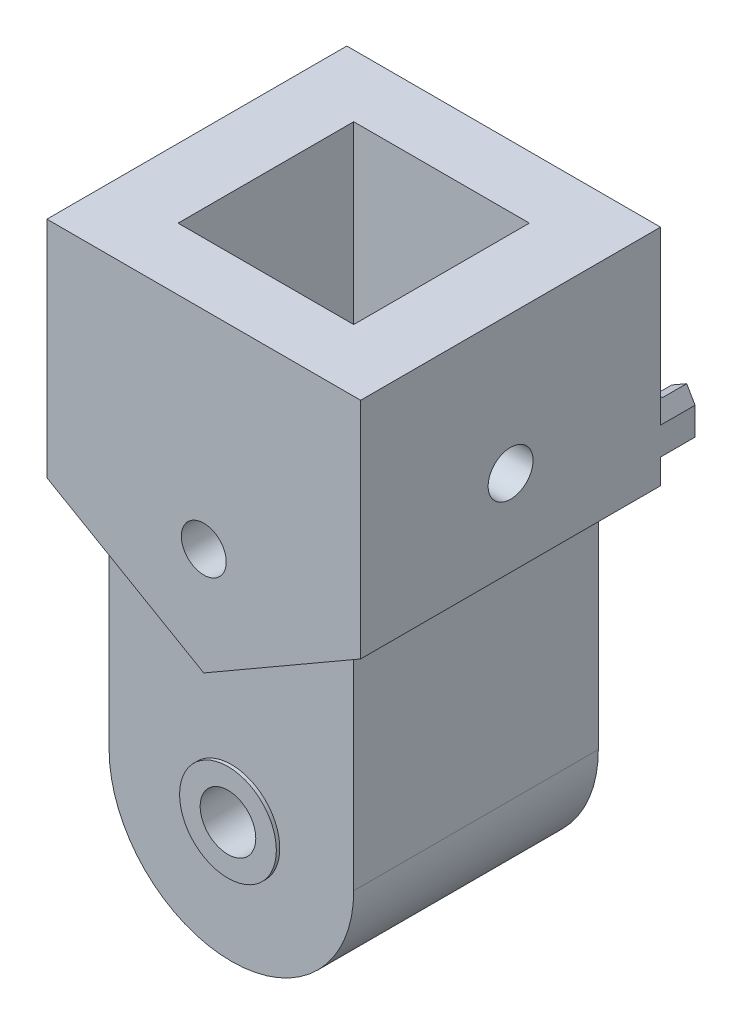
SolidWorks part; units mm, degrees
material "PETG"
ref_plane "Front Plane" through (0, 0, 0) normal (0, 0, 1) x (1, 0, 0)
ref_plane "Top Plane" through (0, 0, 0) normal (0, 1, 0) x (1, 0, 0)
ref_plane "Right Plane" through (0, 0, 0) normal (1, 0, 0) x (0, 0, -1)
sketch "Sketch1" plane through (0, 0, 0) normal (0, 1, 0) x (1, 0, 0)
  line L1 (-12.71, -12.71) -> (12.71, -12.71)
  line L2 (-12.71, -12.71) -> (-12.71, 12.71)
  line L3 (-12.71, 12.71) -> (12.71, 12.71)
  line L4 (12.71, -12.71) -> (12.71, 12.71)
  line L5 (-17.7, -17.7) -> (17.7, -17.7)
  line L6 (-17.7, -17.7) -> (-17.7, 17.7)
  line L7 (-17.7, 17.7) -> (17.7, 17.7)
  line L8 (17.7, -17.7) -> (17.7, 17.7)
  point P8 (0, -17.7)
  point P9 (0, -12.71)
  point P12 (-17.7, 0)
  point P13 (-12.71, 0)
  dimension "D1" = 25.42
  dimension "D2" = 35.4
extrude "Boss-Extrude1" add sketch "Sketch1" along normal blind 50.005
extrude "Boss-Extrude2" add sketch "Sketch1<3>" against normal blind 9.995 contours L1 L4 L3 L2 | L5 L8 L7 L6 L4 L1 L2 L3 region at (0, 0, 0) region at (-17.1994, 0, 0)
sketch "Sketch1<3>" plane through (0, 0, 0) normal (0, 1, 0) x (1, 0, 0) same geometry as "Sketch1"
sketch "Sketch2" plane through (0, 0, -17.7) normal (0, 0, 1) x (1, 0, 0)
  line L1 (17.7, 50.005) -> (17.7, -9.995) construction
  line L4 (-17.7, -9.995) -> (17.7, -9.995) construction
  line L5 (-17.7, -15.97) -> (-17.7, -9.995)
  line L6 (17.7, -9.995) -> (17.7, -15.97)
  line L7 (17.7, -9.995) -> (-17.7, -9.995)
  circle A0 centre (0, -15.995) radius 4.025
  circle A2 centre (0, -15.995) radius 11 construction
  arc A3 (17.7, -15.97) -> (-17.7, -15.97) centre (0, -15.97) cw
  dimension "D1" = 8.05
  dimension "D3" = 22
  dimension "D2" = 6
  dimension "D4" = 5.975
extrude "Boss-Extrude5" add sketch "Sketch2" along normal up to surface (35.4 mm away) up to face at (0, 20.005, 17.7)
ref_plane "Plane1" through (0, -33.67, 0) normal (0, -1, 0) x (-1, 0, 0)
sketch "Sketch3" plane through (0, -33.67, 0) normal (0, -1, 0) x (-1, 0, 0)
  circle A0 centre (0, 0) radius 3.15
  dimension "D1" = 6.3
extrude "Cut-Extrude1" cut sketch "Sketch3" against normal through all
sketch "Sketch4" plane through (0, -33.67, 0) normal (0, -1, 0) x (-1, 0, 0)
  circle A0 centre (0, 0) radius 5.5
  dimension "D1" = 11
extrude "Cut-Extrude2" cut sketch "Sketch4" against normal offset from surface (25.67 mm away) 8 up to face at (0, 0, 3.15)
sketch "Sketch5" plane through (0, 0, 17.7) normal (0, 0, 1) x (1, 0, 0)
  circle A0 centre (0, -15.995) radius 7
  circle A1 centre (0, -15.995) radius 4.025 construction
  circle M6 centre (0, -15.995) radius 4.025
  dimension "D1" = 14
extrude "Boss-Extrude6" add sketch "Sketch5" along normal blind 0.5 contours A0 M6 region at (-6.802, -15.995, 17.7)
mirror "Mirror1" about plane through (0, 0, 0) normal (0, 0, 1) of "Boss-Extrude6"
sketch "Sketch6" plane through (0, 0, 17.7) normal (0, 0, 1) x (1, 0, 0)
  line L5 (8.855, -31.3073) -> (52.1563, -6.3073) construction
  line L6 (-8.855, -0.6327) -> (34.4463, 24.3673) construction
  line L7 (52.1563, -6.3073) -> (34.4463, 24.3673) construction
  line L8 (0, -16) -> (0, -79.4793) construction
  line L9 (17.7, 50.005) -> (17.7, -15.97) construction
  line L10 (17.7, 14.6988) -> (-17.7, 14.6988)
  line L11 (17.7, 14.6988) -> (17.7, 50.005)
  line L12 (17.7, 50.005) -> (-17.7, 50.005)
  line L13 (-17.7, 14.6988) -> (-17.7, 50.005)
  line L14 (17.7, 14.6988) -> (0, 4.4797)
  line L15 (0, 4.4797) -> (-17.7, 14.6988)
  circle A1 centre (0, -15.97) radius 17.71
  arc A2 (-17.7, -15.97) -> (17.7, -15.97) centre (0, -15.97) ccw construction
  line M4 (-17.7, 50.005) -> (-17.7, -15.97)
  line M6 (17.7, -15.97) -> (17.7, 50.005)
  line M7 (17.7, 50.005) -> (-17.7, 50.005)
  dimension "D1" = 50
  dimension "D2" = 120
  dimension "D3" = 35.42
extrude "Boss-Extrude7" add sketch "Sketch6" along normal blind 4 contours L14 L10 M4 | L10 M6 M7 M4 region at (0, 11.2925, 17.7) region at (0, 32.3519, 17.7)
sketch "Sketch7" plane through (0, 0, 21.7) normal (0, 0, 1) x (1, 0, 0)
  line L0 (17.7, 50.005) -> (-17.7, 50.005) construction
  line L1 (17.7, 20.005) -> (0, 20.005) construction
  line L2 (17.7, 14.6988) -> (17.7, 50.005) construction
  line L3 (0, 20.005) -> (-17.7, 20.005) construction
  line L4 (-17.7, 50.005) -> (-17.7, 14.6988) construction
  circle A0 centre (0, 20.005) radius 3.25
  dimension "D1" = 30
  dimension "D2" = 6.5
extrude "Cut-Extrude3" cut sketch "Sketch7" against normal up to next
mirror "Mirror2" about plane through (0, 0, 0) normal (0, 0, 1) of "Boss-Extrude7", "Cut-Extrude3"
sketch "Sketch9" plane through (0, 0, 0) normal (0, 0, 1) x (1, 0, 0)
  line L0 (-17.7, 14.6988) -> (-22.7, 17.5856)
  line L1 (0, 4.4797) -> (-17.7, 14.6988) construction
  line L3 (-17.7, 14.6988) -> (-17.7, 50.005)
  line L4 (-17.7, 50.005) -> (-22.7, 50.005)
  line L5 (-22.7, 17.5856) -> (-22.7, 50.005)
  line L6 (0, 0) -> (0, 50000) construction
  line L7 (22.7, 17.5856) -> (22.7, 50.005)
  line L8 (17.7, 50.005) -> (22.7, 50.005)
  line L9 (17.7, 14.6988) -> (17.7, 50.005)
  line L10 (17.7, 14.6988) -> (22.7, 17.5856)
  dimension "D1" = 5
extrude "Boss-Extrude9" add sketch "Sketch9" along normal up to surface and the other way up to surface up to face at (3.25, 20.005, 21.7) other way up to face at (3.25, 20.005, -21.7)
sketch "Sketch10" plane through (0, 0, 0) normal (-1, 0, 0) x (0, 0, 1)
  line L0 (21.7, 50.005) -> (-21.7, 50.005) construction
  circle A0 centre (0, 30.005) radius 3.25
  dimension "D1" = 6.5
  dimension "D2" = 20
extrude "Cut-Extrude4" cut sketch "Sketch10" against normal through all both and the other way through all
sketch "Sketch11" plane through (0, 0, -21.7) normal (0, 0, -1) x (-1, 0, 0)
  line L0 (-12.9904, 11.9797) -> (-24.2574, 18.4847)
  line L1 (-12.9904, 11.9797) -> (-9.4879, 18.0463)
  line L2 (-24.2574, 18.4847) -> (-20.7549, 24.5513)
  line L3 (-9.4879, 18.0463) -> (-20.7549, 24.5513)
  line L4 (-22.7, 17.5856) -> (0, 4.4797) construction
  line L5 (-12.9904, 11.9797) -> (-11.2583, 10.9797)
  line L6 (-11.2583, 10.9797) -> (-6.7558, 18.7783)
  line L7 (-6.7558, 18.7783) -> (-8.9209, 20.0283)
  line L8 (-8.9209, 20.0283) -> (-9.9209, 18.2963)
  line L9 (-12.9904, 11.9797) -> (-11.2583, 10.9797)
  line L10 (-20.3219, 24.3013) -> (-19.3219, 26.0333)
  line L11 (-19.3219, 26.0333) -> (-21.4869, 27.2833)
  line L12 (-21.4869, 27.2833) -> (-22.7, 25.1822)
  line L13 (-22.7, 17.5856) -> (-22.7, 50.005) construction
  line L14 (-22.7, 25.1822) -> (-22.7, 21.1822)
  line L15 (-18.5855, 23.2988) -> (-16.8534, 22.2988)
  line L16 (-18.5855, 23.2988) -> (-17.5855, 25.0308)
  line L17 (-16.8534, 22.2988) -> (-15.8534, 24.0308)
  line L18 (-17.5855, 25.0308) -> (-15.8534, 24.0308)
  line L19 (-13.3893, 20.2988) -> (-11.6573, 19.2988)
  line L20 (-13.3893, 20.2988) -> (-12.3893, 22.0308)
  line L21 (-11.6573, 19.2988) -> (-10.6573, 21.0308)
  line L22 (-12.3893, 22.0308) -> (-10.6573, 21.0308)
  line L23 (-11.1573, 20.1648) -> (-9.4209, 19.1623) construction
  line L24 (-19.8219, 25.1673) -> (-18.0855, 24.1648) construction
  line L25 (-19.3219, 26.0333) -> (-8.9209, 20.0283)
  point P4 (0, 4.4797)
  point P19 (-16.7195, 24.5308)
  point P30 (-11.5233, 21.5308)
  line M19 (-22.7, 50.005) -> (-22.7, 17.5856)
  line M20 (-22.7, 17.5856) -> (0, 4.4797)
  dimension "D1" = 13.01
  dimension "D2" = 7.005
  dimension "D3" = 15
  dimension "D4" = 2
  dimension "D5" = 0.5
  dimension "D6" = 0.5
  dimension "D7" = 2
  dimension "D8" = 2
  dimension "D9" = 6
extrude "Boss-Extrude10" add sketch "Sketch11" along normal blind 5 contours L11 L12 L2 L3 L10 M19 | L7 L8 L3 L1 L6 M20 region at (9.8379, 15.5715, -21.7) region at (21.4327, 24.861, -21.7)
extrude "Boss-Extrude11" add sketch "Sketch11<3>" along normal blind 1.5 contours L25 L17 L3 L20 | L18 L16 L3 L17 | L25 L10 L3 L16 | L22 L20 L3 L21 | L25 L21 L3 L8 region at (10.2891, 19.6635, -21.7) region at (12.0233, 20.6648, -21.7) region at (18.9537, 24.666, -21.7) region at (14.6214, 22.1648, -21.7) region at (17.2195, 23.6648, -21.7)
sketch "Sketch11<3>" plane through (0, 0, -21.7) normal (0, 0, -1) x (-1, 0, 0) same geometry as "Sketch11"
chamfer "Chamfer1" distance 1.5 angle 45 1 edges at (14.1214, 23.0308, -21.7)
mirror "Mirror3" about plane through (0, 0, 0) normal (1, 0, 0) of "Boss-Extrude11", "Chamfer1", "Boss-Extrude10"
equation "\"tol_dia_id_intfc\" = 0.0200mm ' For hole diameters - Interference fit"
equation "\"tol_dia_id_slip\"  = 0.0300mm ' For hole diameters - Slip fit"
equation "\"tol_dia_id_clear\" = 0.0500mm ' For hole diameters - Clearance fit"
equation "\"tol_dia_od_intfc\" = 0.0200mm ' For shaft diameters - Interference fit"
equation "\"tol_dia_od_slip\"  = 0.0300mm ' For shaft diameters - Slip fit"
equation "\"tol_dia_od_clear\" = 0.0500mm ' For shaft diameters - Clearance fit"
equation "\"tol_general_intfc\"= 0.0030mm ' For general parts (Horiz) - Interference fit"
equation "\"tol_general_slip\" = 0.0050mm ' For general parts (Horiz) - Slip fit"
equation "\"tol_general_clear\"= 0.0100mm ' For general parts (Horiz) - Clearance fit"
equation "\"tol_layer_intfc\"  = 0.0030mm ' For all parts (Vert) - Interference fit"
equation "\"tol_layer_slip\"   = 0.0050mm ' For all parts (Vert) - Slip fit"
equation "\"tol_layer_clear\"  = 0.0100mm ' For all parts (Vert) - Clearance fit"
equation "\"tol_corner_rad\"   = 0.100mm ' For corners that fit into other parts"
equation "\"D1@Sketch1\"= 25.40mm + \"tol_general_clear\" * 2"
equation "\"D2@Sketch1\"=25.4+10"
equation "\"D1@Boss-Extrude1\"= 50.00mm + \"tol_layer_slip\""
equation "\"D1@Boss-Extrude2\"=10.00mm-\"tol_layer_slip\""
equation "\"D1@Sketch2\"=8.00mm+\"tol_dia_id_clear\""
equation "\"D4@Sketch2\"=6.00mm-\"tol_dia_od_clear\"/2"
equation "\"D3@Sketch6\"=25.4+10+\"tol_general_clear\"*2"
equation "\"D1@Sketch11\"=13mm+\"tol_general_slip\"*2"
equation "\"D2@Sketch11\"=7mm+\"tol_general_slip\""
equation "\"D6@Sketch11\"=\"D5@Sketch11\""
equation "\"D8@Sketch11\"=\"D7@Sketch11\""
